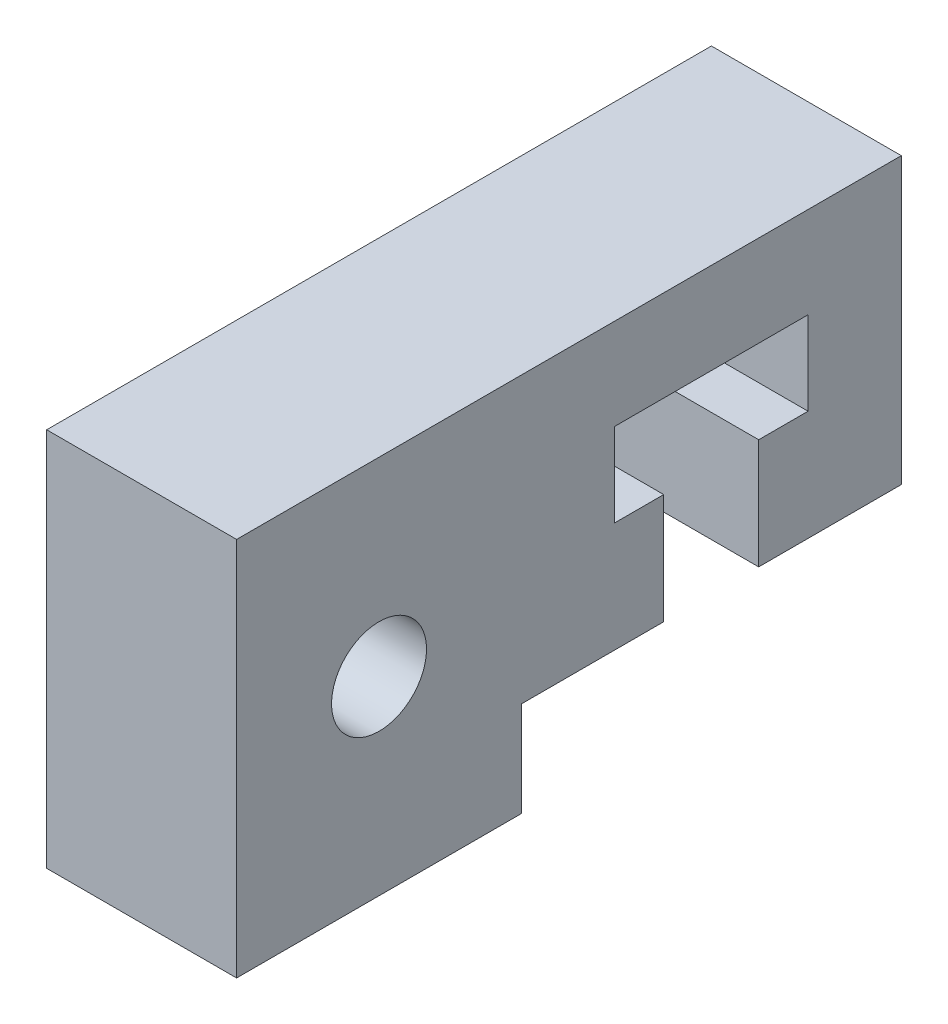
SolidWorks part; units mm, degrees
ref_plane "Front Plane" through (0, 0, 0) normal (0, 0, 1) x (1, 0, 0)
ref_plane "Top Plane" through (0, 0, 0) normal (0, 1, 0) x (1, 0, 0)
ref_plane "Right Plane" through (0, 0, 0) normal (1, 0, 0) x (0, 0, -1)
sketch "Sketch2" plane through (0, 0, 0) normal (1, 0, 0) x (0, 0, -1)
  line L0 (-4.7625, 6.35) -> (-4.7625, -6.35)
  line L1 (-4.7625, -6.35) -> (4.7625, -6.35)
  line L2 (4.7625, -6.35) -> (4.7625, -3.175)
  line L3 (17.4625, -3.175) -> (12.6942, -3.175)
  line L4 (17.4625, -3.175) -> (17.4625, 6.35)
  line L5 (17.4625, 6.35) -> (-4.7625, 6.35)
  line L6 (-19.474, 0) -> (-4.2216, 0) construction
  line L7 (12.6942, -3.175) -> (12.6942, 0.508)
  line L8 (12.6942, 0.508) -> (14.3452, 0.508)
  line L9 (14.3452, 0.508) -> (14.3452, 3.302)
  line L10 (14.3452, 3.302) -> (7.8682, 3.302)
  line L11 (7.8682, 3.302) -> (7.8682, 0.508)
  line L12 (7.8682, 0.508) -> (9.5192, 0.508)
  line L13 (9.5192, 0.508) -> (9.5192, -3.175)
  line L14 (9.5192, -3.175) -> (4.7625, -3.175)
  line L15 (11.1067, 0.9915) -> (11.1067, -22.7495) construction
  circle A0 centre (0, 0) radius 1.5875
  point P10 (-4.7625, 0)
  point P21 (11.1067, 3.302)
  dimension "D2" = 3.175
  dimension "D1" = 12.7
  dimension "D3" = 12.7
  dimension "D4" = 9.525
  dimension "D5" = 4.7625
  dimension "D6" = 22.225
  dimension "D7" = 6.477
  dimension "D8" = 3.175
  dimension "D9" = 6.3558
  dimension "D10" = 6.477
  dimension "D11" = 2.794
  dimension "D12" = 3.175
extrude "Boss-Extrude1" add sketch "Sketch2" along normal blind 3.175 and the other way blind 3.175
